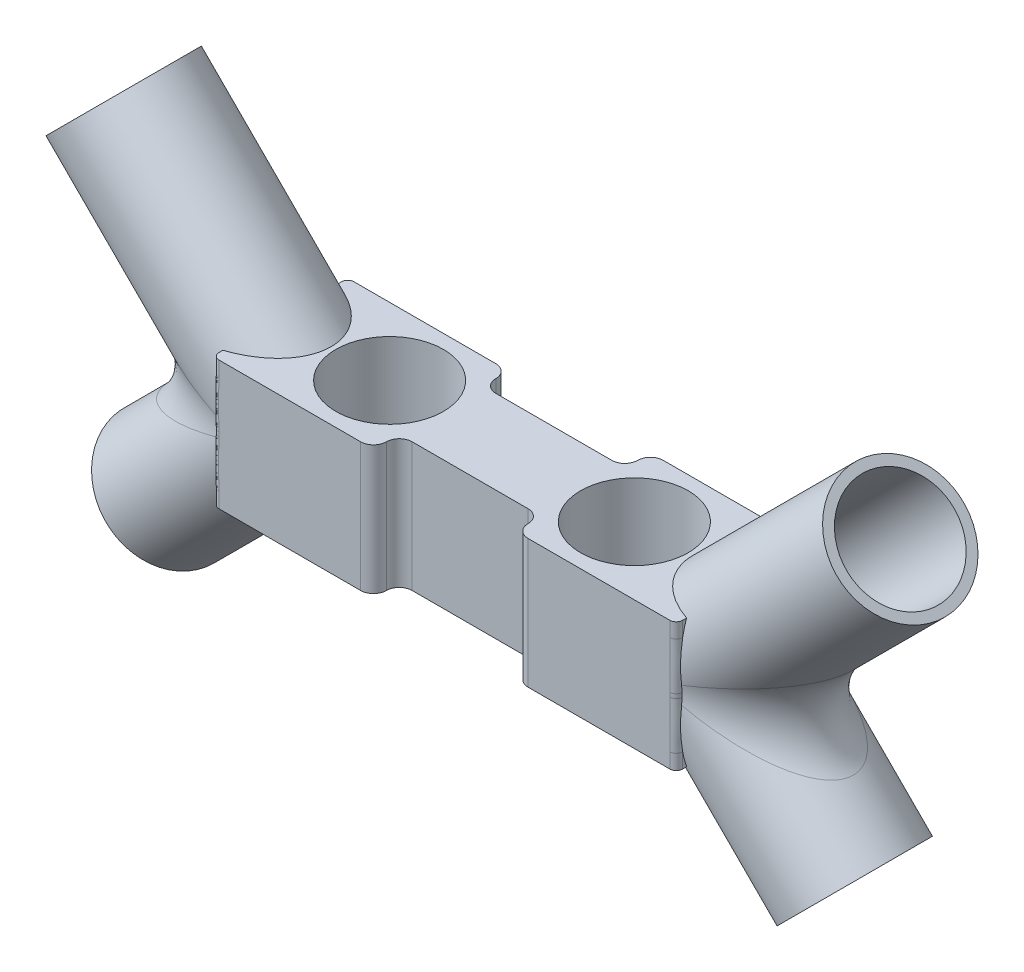
SolidWorks part; units mm, degrees
ref_plane "Alzado" through (0, 0, 0) normal (0, 0, 1) x (1, 0, 0)
ref_plane "Planta" through (0, 0, 0) normal (0, 1, 0) x (1, 0, 0)
ref_plane "Vista lateral" through (0, 0, 0) normal (1, 0, 0) x (0, 0, -1)
sketch "Croquis1" plane through (0, 0, 0) normal (0, 1, 0) x (1, 0, 0)
  line L0 (0, 0) -> (-36, 0) construction
  line L1 (-11, 6.5) -> (11, 6.5)
  line L3 (-11, -6.5) -> (11, -6.5)
  line L5 (-11, 6.5) -> (11, -6.5) construction
  line L6 (-11, -6.5) -> (11, 6.5) construction
  line L7 (-36, -10.5) -> (-36, 10.5)
  line L10 (0, 0) -> (0, -6.5) construction
  line L12 (36, -10.5) -> (36, 10.5)
  line L14 (-36, 10.5) -> (-11, 10.5)
  line L15 (-11, 10.5) -> (-11, 6.5)
  line L16 (-36, -10.5) -> (-11, -10.5)
  line L17 (-11, -10.5) -> (-11, -6.5)
  line L18 (36, 10.5) -> (11, 10.5)
  line L19 (11, 10.5) -> (11, 6.5)
  line L20 (36, -10.5) -> (11, -10.5)
  line L21 (11, -10.5) -> (11, -6.5)
  point P4 (0, 0)
  point P14 (-36, 0)
  point P16 (0, 6.5)
  dimension "D1" = 25
  dimension "D4" = 21
  dimension "D2" = 22
  dimension "D3" = 13
extrude "Saliente-Extruir2" add sketch "Croquis1" along normal mid plane 20
sketch "Croquis2" plane through (0, 0, 0) normal (0, 1, 0) x (1, 0, 0)
  line L0 (-36, -5) -> (-50.1421, -19.1421)
  line L2 (-36, -5) -> (-36, 5)
  line L3 (36, -5) -> (36, 5)
  line L4 (36, -10.5) -> (36, 10.5) construction
  line L5 (36, -5) -> (50.1421, -19.1421)
  line L6 (36, 5) -> (50.1421, 19.1421)
  line L7 (0, 0) -> (0, -6.5) construction
  line L8 (-11, -6.5) -> (11, -6.5) construction
  line L9 (-36, 5) -> (-50.1421, 19.1421)
  point P15 (36, 0)
  dimension "D2" = 10
  dimension "D5" = 45
  dimension "D6" = 45
  dimension "D7" = 20
ref_plane "Plano1" through (50.1421, 0, 0) normal (1, 0, 0) x (0, 0, -1)
sketch "Croquis22" plane through (0, 0, 0) normal (0, 0, 1) x (1, 0, 0)
  line L0 (-60.2843, 28.2843) -> (-32, 0)
  line L1 (-32, 0) -> (-53.2132, -21.2132)
  line L2 (-32, 0) -> (-36, 0) construction
  line L3 (-36, 10) -> (-36, -10) construction
  line L4 (32, 0) -> (53.2132, -21.2132)
  line L5 (60.2843, 28.2843) -> (32, 0)
  line L6 (0, 0) -> (0, -10) construction
  line L7 (-11, -10) -> (11, -10) construction
  dimension "D6" = 45
  dimension "D2" = 45
  dimension "D3" = 40
  dimension "D4" = 4
  dimension "D5" = 30
ref_plane "Plano2" through (-60.2843, 28.2843, 0) normal (0.7071, -0.7071, 0) x (-0.7071, -0.7071, 0)
sketch "Croquis33" plane through (-60.2843, 28.2843, 0) normal (0.7071, -0.7071, 0) x (-0.7071, -0.7071, 0)
  circle A0 centre (0, 0) radius 9.85
  dimension "D1" = 19.7
ref_plane "Plano3" through (60.2843, 28.2843, 0) normal (-0.7071, -0.7071, 0) x (0, 0, 1)
sketch "Croquis34" plane through (60.2843, 28.2843, 0) normal (-0.7071, -0.7071, 0) x (0, 0, 1)
  circle A0 centre (0, 0) radius 9.85
  dimension "D2" = 19.7
sketch "Croquis35" plane through (0, 0, 0) normal (0, 1, 0) x (1, 0, 0)
  line L0 (-19, 0) -> (19, 0) construction
  circle A0 centre (-19, 0) radius 8.35
  circle A1 centre (19, 0) radius 8.35
  point P4 (0, 0)
  dimension "D1" = 16.7
  dimension "D2" = 38
extrude "Cortar-Extruir1" cut sketch "Croquis35" against normal mid plane 30 contours A1 | A0
extrude "Saliente-Extruir3" add sketch "Croquis33" along normal up to body separate body
extrude "Saliente-Extruir5" add sketch "Croquis34" along normal up to body separate body
ref_plane "Plano4" through (-53.2132, -21.2132, 0) normal (-0.7071, -0.7071, 0) x (0, 0, 1)
ref_plane "Plano5" through (53.2132, -21.2132, 0) normal (0.7071, -0.7071, 0) x (0, 0, -1)
sketch "Croquis36" plane through (-53.2132, -21.2132, 0) normal (-0.7071, -0.7071, 0) x (0, 0, 1)
  circle A0 centre (0, 0) radius 9.85
  dimension "D2" = 19.7
extrude "Saliente-Extruir6" add sketch "Croquis36" against normal up to body separate body
sketch "Croquis37" plane through (53.2132, -21.2132, 0) normal (0.7071, -0.7071, 0) x (0, 0, -1)
  circle A0 centre (0, 0) radius 9.85
  dimension "D1" = 19.7
extrude "Saliente-Extruir7" add sketch "Croquis37" against normal up to body separate body
fillet "Redondeo2" radius 2 8 edges at (11, 0, -10.5) (11, 0, -6.5) (-11, 0, -6.5) (-11, 0, -10.5) (11, 0, 6.5) (11, 0, 10.5) (-11, 0, 6.5) (-11, 0, 10.5)
fillet "Redondeo4" radius 1 4 edges at (-36, 0, 10.5) (36, 0, 10.5) (-36, 0, -10.5) (36, 0, -10.5)
sketch "Croquis38" plane through (-44.2843, 44.2843, 0) normal (-0.7071, 0.7071, 0) x (0, 0, 1)
  circle A0 centre (0, -22.6274) radius 8.35
  circle A1 centre (0, -22.6274) radius 9.85
  circle A2 centre (0, -22.6274) radius 9.85
  dimension "D2" = 1.5
  dimension "D1" = 0
extrude "Cortar-Extruir3" cut sketch "Croquis38" against normal blind 30 contours A0
sketch "Croquis40" plane through (-37.2132, -37.2132, 0) normal (-0.7071, -0.7071, 0) x (0, 0, 1)
  circle A0 centre (0, 22.6274) radius 8.35
  circle A1 centre (0, 22.6274) radius 9.85
  circle A2 centre (0, 22.6274) radius 9.85
  dimension "D2" = 1.5
  dimension "D1" = 0
extrude "Cortar-Extruir4" cut sketch "Croquis40" against normal blind 20 contours A0
sketch "Croquis41" plane through (44.2843, 44.2843, 0) normal (0.7071, 0.7071, 0) x (0, 0, -1)
  circle A0 centre (0, -22.6274) radius 8.35
  circle A1 centre (0, -22.6274) radius 9.85
  circle A2 centre (0, -22.6274) radius 9.85
  dimension "D2" = 1.5
  dimension "D1" = 0
extrude "Cortar-Extruir5" cut sketch "Croquis41" against normal blind 30 contours A0
sketch "Croquis42" plane through (37.2132, -37.2132, 0) normal (0.7071, -0.7071, 0) x (0, 0, -1)
  circle A0 centre (0, 22.6274) radius 8.35
  circle A1 centre (0, 22.6274) radius 9.85 construction
  circle A2 centre (0, 22.6274) radius 9.85
  dimension "D1" = 1.5
extrude "Cortar-Extruir6" cut sketch "Croquis42" against normal blind 20 contours A0
fillet "Redondeo6" radius 10 1 edges at (-45.93, 0, 0) type face fillet first side face at (-53.3193, 35.2493, 0) second side face at (-46.2482, -28.1782, 0)
fillet "Redondeo7" radius 10 1 edges at (45.93, 0, 0) type face fillet first side face at (67.2493, 21.3193, 0) second side face at (60.1782, -14.2482, 0)
